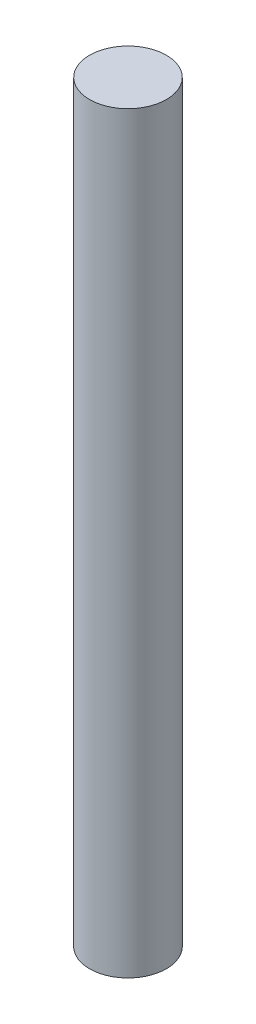
SolidWorks part; units mm, degrees
material "6061-T4 (SS)"
ref_plane "Front Plane" through (0, 0, 0) normal (0, 0, 1) x (1, 0, 0)
ref_plane "Top Plane" through (0, 0, 0) normal (0, 1, 0) x (1, 0, 0)
ref_plane "Right Plane" through (0, 0, 0) normal (1, 0, 0) x (0, 0, -1)
sketch "Sketch1" plane through (0, 0, 0) normal (0, 1, 0) x (1, 0, 0)
  circle A0 centre (0, 0) radius 5
  dimension "D1" = 10
extrude "Boss-Extrude1" add sketch "Sketch1" along normal blind 98
equation "\"D1@Boss-Extrude1\"=98"
